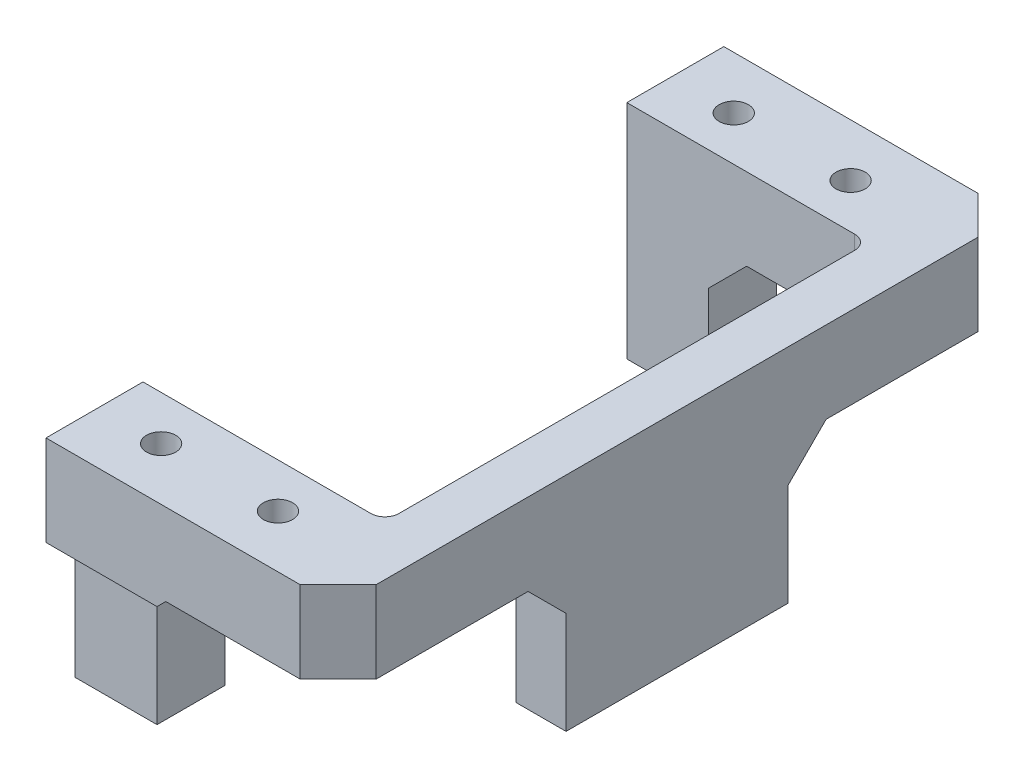
SolidWorks part; units mm, degrees
ref_plane "Plan de face" through (0, 0, 0) normal (0, 0, 1) x (1, 0, 0)
ref_plane "Plan de dessus" through (0, 0, 0) normal (0, 1, 0) x (1, 0, 0)
ref_plane "Plan de droite" through (0, 0, 0) normal (1, 0, 0) x (0, 0, -1)
sketch "Esquisse1" plane through (0, 0, 0) normal (0, 1, 0) x (1, 0, 0)
  line L0 (-9.5, 20.7) -> (-9.5, 26.5)
  line L1 (-9.5, 26.5) -> (15.5, 26.5)
  line L2 (15.5, 26.5) -> (15.5, -26.5)
  line L3 (15.5, -26.5) -> (-9.5, -26.5)
  line L4 (-9.5, -26.5) -> (-9.5, -20.7)
  line L5 (-9.5, -20.7) -> (10, -20.7)
  line L6 (11.2, -19.5) -> (11.2, 19.5)
  line L7 (10, 20.7) -> (-9.5, 20.7)
  line L8 (-8.3, -20.5) -> (10, -20.5) construction
  line L9 (11, -19.5) -> (11, 19.5) construction
  line L10 (10, 20.5) -> (-8.3, 20.5) construction
  line L11 (-9.5, -20.5) -> (10, -20.5) construction
  line L12 (11, -19.5) -> (11, 19.5) construction
  line L13 (10, 20.5) -> (-9.5, 20.5) construction
  arc A0 (10, -20.7) -> (11.2, -19.5) centre (10, -19.5) ccw
  arc A1 (11.2, 19.5) -> (10, 20.7) centre (10, 19.5) ccw
  arc A2 (10, -20.5) -> (11, -19.5) centre (10, -19.5) ccw construction
  arc A3 (11, 19.5) -> (10, 20.5) centre (10, 19.5) ccw construction
  arc A4 (10, -20.5) -> (11, -19.5) centre (10, -19.5) ccw construction
  arc A5 (11, 19.5) -> (10, 20.5) centre (10, 19.5) ccw construction
  point P4 (-9.2512, -20.5)
  point P10 (15.5, 0)
  point P11 (-17.32, 34.9758)
  point P12 (-17.5773, -35.2399)
  point P14 (-9.5, -20.5)
  point P17 (0, 0)
  point P18 (-9.5, 20.5)
  point P20 (0, 0)
  point P23 (-9.5, 20.5)
  point P25 (0, 0)
  point P30 (-9.5, 20.5)
  point P31 (0, 0)
  point P35 (-9.5, -20.7)
  point P36 (0, 0)
  point P37 (-9.5, 20.8912)
  dimension "D1" = 9.5
  dimension "D2" = 0.2
  dimension "D3" = 53
  dimension "D4" = 25
extrude "Boss.-Extru.1" add sketch "Esquisse1" along normal blind 19
sketch "Esquisse2" plane through (0, 0, 0) normal (0, -1, 0) x (1, 0, 0)
  line L0 (-9.5, 20.7) -> (-9.5, 26.5) construction
  line L1 (15.5, 26.5) -> (-2.5, 26.5)
  line L2 (15.5, 26.5) -> (15.5, 9.5)
  line L3 (15.5, 9.5) -> (-2.5, 9.5)
  line L4 (-2.5, 26.5) -> (-2.5, 9.5)
  line L5 (-17.7333, 0) -> (16.2166, 0) construction
  line L6 (-2.5, -26.5) -> (-2.5, -9.5)
  line L7 (15.5, -9.5) -> (-2.5, -9.5)
  line L8 (15.5, -26.5) -> (15.5, -9.5)
  line L9 (15.5, -26.5) -> (-2.5, -26.5)
  dimension "D1" = 19
  dimension "D2" = 7
extrude "Enlèv. mat.-Extru.1" cut sketch "Esquisse2" against normal blind 12
hole_wizard "Trou taraudé M31" positions "Esquisse6" profile "Esquisse5" tap size "M3" standard "ISO"
sketch "Esquisse6" plane through (0, 0, 0) normal (0, -1, 0) x (-1, 0, 0)
  line L0 (-11.2, -9.5) -> (-15.5, -9.5) construction
  line L1 (1.5, -19.75) -> (9.5, -19.75) construction
  line L2 (9.5, -20.7) -> (9.5, -26.5) construction
  line L3 (-9.5, 9.5) -> (-9.5, -9.5) construction
  line L4 (9.5, 26.5) -> (9.5, 20.7) construction
  point P0 (5.5, 23.6)
  point P2 (-13.35, 0)
  point P4 (5.5, -23.6)
  point P9 (-13.35, -9.5)
  point P13 (5.5, -19.75)
  point P16 (9.5, -23.6)
  point P20 (-9.5, 0)
  point P24 (9.5, 23.6)
cosmetic thread "Filetage de perçage1"
cosmetic thread "Filetage de perçage2"
cosmetic thread "Filetage de perçage3"
sketch "Esquisse5" plane through (-5.5, 0, -23.6) normal (1, 0, 0) x (0, 0, -1)
  line L0 (0, 0) -> (0, 9.2511)
  line L1 (0, 9.2511) -> (1.25, 8.5)
  line L2 (1.25, 8.5) -> (1.25, 0)
  line L5 (1.25, 0) -> (0, 0)
  line L10 (0, 9.2511) -> (-1.25, 8.5) construction
  line L11 (0, -6.35) -> (0, 107.95) construction
  dimension "Diamètre du trou pour taraudage" = 2.5
  dimension "Profondeur du trou pour taraudage" = 8.5
  dimension "Angle de pointe" = 118
sketch "Esquisse7" plane through (0, 19, 0) normal (0, 1, 0) x (1, 0, 0)
  line L0 (21.2214, 0) -> (-14.9227, 0) construction
  line L1 (15.5, -26.5) -> (15.5, 26.5) construction
  line L2 (-9.5, -20.7) -> (15.5, -20.7)
  line L3 (-9.5, -20.7) -> (-9.5, -29)
  line L4 (-9.5, -29) -> (15.5, -29)
  line L5 (15.5, -20.7) -> (15.5, -29)
  line L6 (15.5, 20.7) -> (15.5, 29)
  line L7 (-9.5, 29) -> (15.5, 29)
  line L8 (-9.5, 20.7) -> (-9.5, 29)
  line L9 (-9.5, 20.7) -> (15.5, 20.7)
  point P14 (-9.5, 20.7)
  dimension "D1" = 58
extrude "Boss.-Extru.2" add sketch "Esquisse7" against normal up to surface (7 mm away) up to face at (8.3784, 12, 19.0212)
chamfer "Chanfrein3" distance 3.25 angle 45 8 edges at (13.35, 12, -9.5) (-6, 12, -26.5) (-2.5, 12, -23.6) (13.35, 12, 9.5) (-6, 12, 26.5) (-2.5, 12, 23.6) (15.5, 15.5, 29) (15.5, 15.5, -29)
hole_wizard "Trou taraudé M32" positions "Esquisse9" profile "Esquisse8" tap size "M3" standard "ISO"
sketch "Esquisse9" plane through (0, 19, 0) normal (0, 1, 0) x (1, 0, 0)
  point P14 (-4.15, 24.5)
  point P17 (-4.15, -24.5)
  point P20 (5.85, -24.5)
  point P23 (5.85, 24.5)
  point P27 (0, 0)
  point P28 (0, 0)
cosmetic thread "Filetage de perçage4" parameters "D1"=6, "D2"=3
cosmetic thread "Filetage de perçage5" parameters "D1"=6, "D2"=3
sketch "Esquisse8" plane through (-4.15, 19, -24.5) normal (1, 0, 0) x (0, 0, 1)
  line L0 (0, 0) -> (0, 6.7511)
  line L1 (0, 6.7511) -> (1.25, 6)
  line L2 (1.25, 6) -> (1.25, 0)
  line L5 (1.25, 0) -> (0, 0)
  line L10 (0, 6.7511) -> (-1.25, 6) construction
  line L11 (0, -6.35) -> (0, 107.95) construction
  dimension "Diamètre du trou pour taraudage" = 2.5
  dimension "Profondeur du trou pour taraudage" = 6
  dimension "Angle de pointe" = 118
cosmetic thread "Filetage de perçage6" parameters "D1"=6, "D2"=3
cosmetic thread "Filetage de perçage7" parameters "D1"=6, "D2"=3
